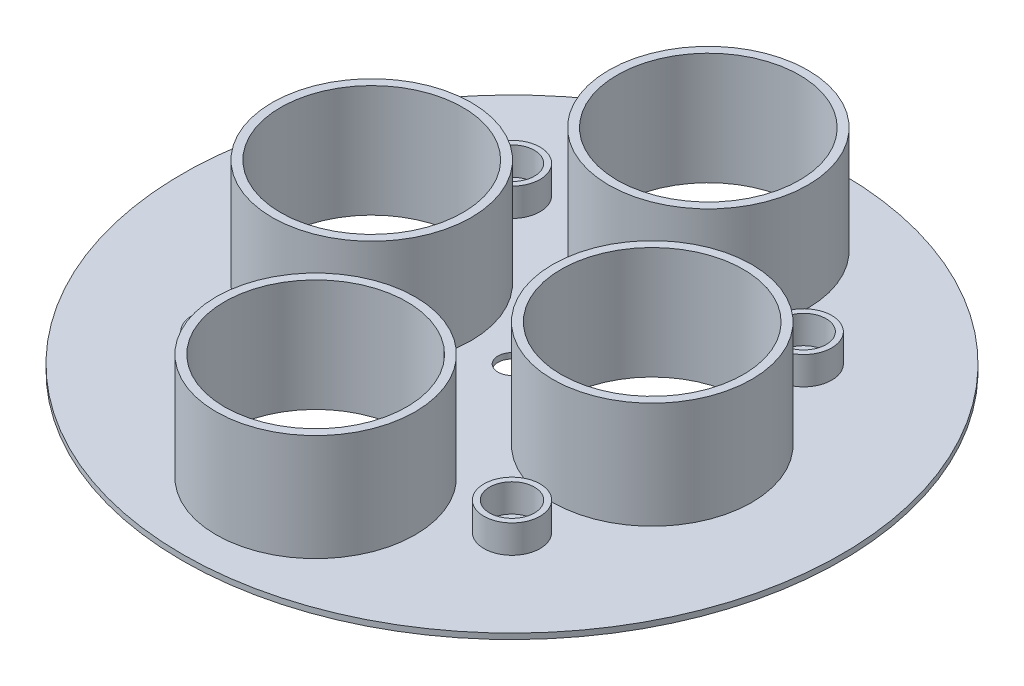
SolidWorks part; units mm, degrees
note: The reader was unsure of these and kept them because the rebuilt part matched: shared geometry of "Çizim1<2>".
ref_plane "Ön Düzlem" through (0, 0, 0) normal (0, 0, 1) x (1, 0, 0)
ref_plane "Üst Düzlem" through (0, 0, 0) normal (0, 1, 0) x (1, 0, 0)
ref_plane "Sağ Düzlem" through (0, 0, 0) normal (1, 0, 0) x (0, 0, -1)
sketch "Çizim1" plane through (0, 0, 0) normal (0, 1, 0) x (1, 0, 0)
  circle A0 centre (0, 0) radius 117.5
  circle A1 centre (0, 70) radius 32.5
  circle A2 centre (50, 0) radius 32.5
  circle A3 centre (0, -70) radius 32.5
  circle A4 centre (-50, 0) radius 32.5
  circle A5 centre (0, 0) radius 5
  dimension "D1" = 65
  dimension "D6" = 235
  dimension "D7" = 10
  dimension "D2" = 50
  dimension "D3" = 50
  dimension "D4" = 70
  dimension "D5" = 70
extrude "Yükseklik-Ekstrüzyon1" add sketch "Çizim1" along normal blind 2
extrude "Ekstrüzyon-İnce1" add sketch "Çizim1<2>" along normal blind 40 thin contours A3 | A4 | A2 | A1
sketch "Çizim1<2>" plane through (0, 0, 0) normal (0, 1, 0) x (1, 0, 0) same geometry as "Çizim1"
sketch "Çizim2" plane through (0, 2, 0) normal (0, 1, 0) x (1, 0, 0)
  circle A1 centre (52, -52) radius 8
  circle A2 centre (-52, -52) radius 8
  circle A3 centre (-52, 52) radius 8
  circle A4 centre (52, 52) radius 8
  point P14 (0, 0)
  dimension "D2" = 52
  dimension "D4" = 16
  dimension "D3" = 52
  dimension "D1" = 4
extrude "Ekstrüzyon-İnce2" add sketch "Çizim2" along normal blind 10 thin
equation "\"D3@Çizim1\"=\"D2@Çizim1\""
equation "\"D5@Çizim1\"=\"D4@Çizim1\""
equation "\"D6@Çizim1\"=\"D5@Çizim1\"+\"D4@Çizim1\"+\"D1@Çizim1\"+30"
